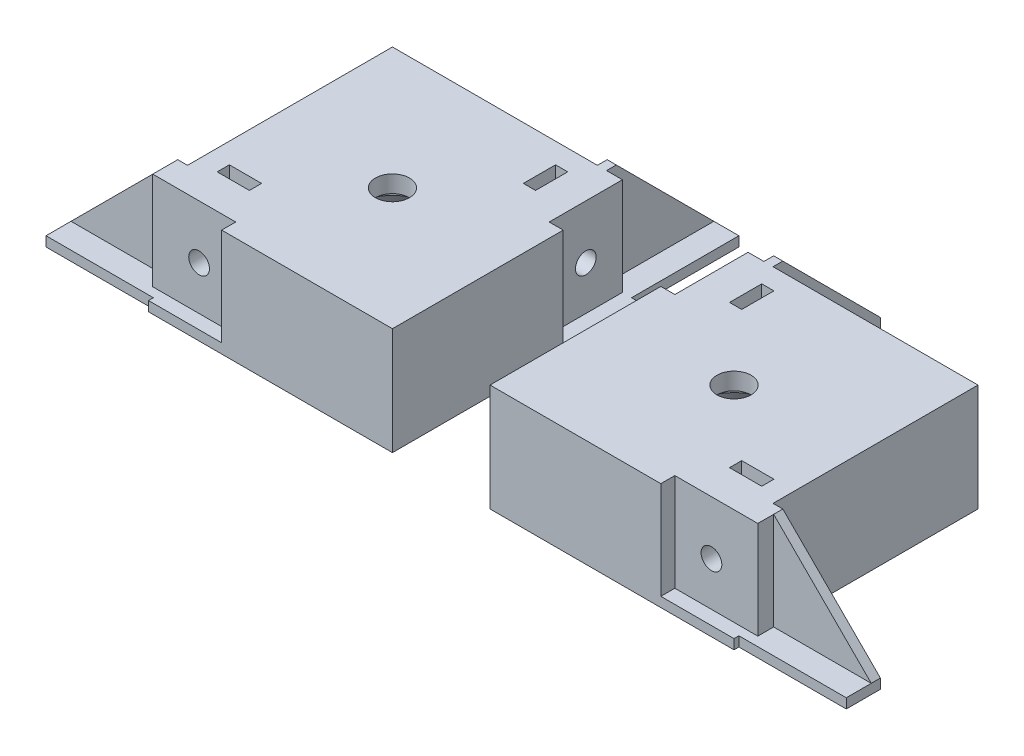
SolidWorks part; units mm, degrees
ref_plane "Front Plane" through (0, 0, 0) normal (0, 0, 1) x (1, 0, 0)
ref_plane "Top Plane" through (0, 0, 0) normal (0, 1, 0) x (1, 0, 0)
ref_plane "Right Plane" through (0, 0, 0) normal (1, 0, 0) x (0, 0, -1)
sketch "Sketch1" plane through (0, 0, 0) normal (0, 1, 0) x (1, 0, 0)
  line L0 (-25, 25) -> (25, -25) construction
  line L1 (-25, 25) -> (25, 25)
  line L2 (-25, 25) -> (-25, -25)
  line L3 (-25, -25) -> (25, -25)
  line L4 (25, 25) -> (25, -25)
  point P4 (0, 0)
  point P8 (0, 0)
  dimension "D1" = 50
extrude "Boss-Extrude1" add sketch "Sketch1" along normal blind 11 and the other way blind 11
sketch "Sketch2" plane through (0, 0, 0) normal (0, 0, 1) x (1, 0, 0)
  line L0 (-25, -11) -> (25, -11) construction
  line L1 (-3.5, 7.5) -> (-3.5, 11)
  line L2 (-3.5, 11) -> (0, 11)
  line L3 (-25, 11) -> (25, 11) construction
  line L5 (-18, -11) -> (-10.5, 4)
  line L6 (-10.5, 4) -> (-8, 4)
  line L7 (-8, 4) -> (-8, 7.5)
  line L8 (-8, 7.5) -> (-3.5, 7.5)
  line L9 (0, 11) -> (0, -11)
  line L10 (0, -11) -> (-18, -11)
  line L11 (-8, 4) -> (-8, -11) construction
  line L12 (-10.5, 4) -> (-10.5, -11) construction
  point P4 (-3.2947, 11)
  point P12 (0, 0)
  dimension "D1" = 8
  dimension "D2" = 18
  dimension "D3" = 3.5
  dimension "D4" = 2.5
  dimension "D5" = 3.5
  dimension "D6" = 3.5
revolve "Cut-Revolve1" cut sketch "Sketch2" angle 360 about L9
sketch "Sketch3" plane through (25, 0, 0) normal (1, 0, 0) x (0, 0, -1)
  line L0 (-25, 11) -> (25, 11) construction
  line L1 (-24, 11) -> (-22.125, 11)
  line L2 (-24, 11) -> (-24, -11)
  line L3 (-24, -11) -> (-17, -11)
  line L4 (-17, 11) -> (-17, -11)
  line L5 (-25, -11) -> (25, -11) construction
  line L6 (-18.875, 11) -> (-17, 11)
  line L7 (-25, -11) -> (-25, 11) construction
  line L8 (-22.125, 11) -> (-22.125, -9)
  line L9 (-22.125, -9) -> (-18.875, -9)
  line L10 (-18.875, 11) -> (-18.875, -9)
  dimension "D1" = 1
  dimension "D2" = 7
  dimension "D3" = 3.25
  dimension "D4" = 2
extrude "Boss-Extrude2" add sketch "Sketch3" along normal blind 22
sketch "Sketch4" plane through (0, 0, 17) normal (0, 0, -1) x (-1, 0, 0)
  line L0 (-47, -9) -> (-27, 11)
  line L1 (-47, -11) -> (-47, 11) construction
  line L2 (-47, 11) -> (-25, 11) construction
  line L3 (-27, 11) -> (-47, 11)
  line L4 (-47, 11) -> (-47, -9)
  dimension "D1" = 20
extrude "Cut-Extrude1" cut sketch "Sketch4" against normal blind 7
sketch "Sketch5" plane through (0, -9, 0) normal (0, 1, 0) x (1, 0, 0)
  line L1 (25, -18.875) -> (27, -18.875)
  line L2 (25, -18.875) -> (25, -22.125)
  line L3 (25, -22.125) -> (27, -22.125)
  line L4 (27, -18.875) -> (27, -22.125)
extrude "Boss-Extrude3" add sketch "Sketch5" along normal blind 20
sketch "Sketch6" plane through (0, 11, 0) normal (0, 1, 0) x (1, 0, 0)
  line L1 (47, -22.125) -> (10, -22.125)
  line L2 (47, -22.125) -> (47, -25)
  line L3 (47, -25) -> (10, -25)
  line L4 (10, -22.125) -> (10, -25)
  line L5 (-25, -25) -> (25, -25) construction
  line L6 (25, -17) -> (25, 25) construction
  point P1 (10.0363, -25)
  dimension "D1" = 15
extrude "Cut-Extrude2" cut sketch "Sketch6" against normal blind 20
sketch "Sketch8" plane through (0, 0, 22.125) normal (0, 0, 1) x (1, 0, 0)
  line L0 (0, 0) -> (17.5, 0) construction
  line L1 (25, -9) -> (17.5, 0) construction
  line L2 (17.5, 0) -> (10, -9) construction
  line L3 (27, 11) -> (10, 11) construction
  line L4 (14.2, -3.3) -> (20.8, -3.3) construction
  line L5 (14.2, -3.3) -> (14.2, 3.3) construction
  line L6 (14.2, 3.3) -> (20.8, 3.3) construction
  line L7 (20.8, -3.3) -> (20.8, 3.3) construction
  line L8 (14.2, -3.3) -> (20.8, 3.3) construction
  line L9 (14.2, 3.3) -> (20.8, -3.3) construction
  circle A0 centre (17.5, 0) radius 2.125
  dimension "D1" = 4.25
  dimension "D2" = 6.6
  dimension "D3" = 14.3
extrude "Cut-Extrude3" cut sketch "Sketch8" against normal blind 6
sketch "Sketch9" plane through (0, 11, 0) normal (0, 1, 0) x (1, 0, 0)
  line L0 (17.5, -12.625) -> (17.5, -22.125) construction
  line L1 (14.2, -12.625) -> (20.8, -12.625)
  line L2 (14.2, -12.625) -> (14.2, -15.125)
  line L3 (14.2, -15.125) -> (20.8, -15.125)
  line L4 (20.8, -12.625) -> (20.8, -15.125)
  line L7 (15.375, -22.125) -> (19.625, -22.125) construction
  line L8 (15.375, -16.125) -> (19.625, -16.125) construction
  point P6 (0, 0)
  dimension "D1" = 6.6
  dimension "D2" = 2.5
  dimension "D3" = 1
extrude "Cut-Extrude4" cut sketch "Sketch9" against normal blind 14.4
sketch "Sketch11" plane through (0, 0, 16.125) normal (0, 0, 1) x (1, 0, 0)
  circle A0 centre (17.5, 0) radius 2
  dimension "D1" = 4
extrude "Cut-Extrude5" cut sketch "Sketch11" against normal blind 8
ref_plane "Plane1" through (0, 0, 0) normal (0.7071, 0, 0.7071) x (0.7071, 0, -0.7071)
mirror "Mirror1" about plane through (0, 0, 0) normal (0.7071, 0, 0.7071) of "Cut-Extrude5", "Cut-Extrude2", "Boss-Extrude2", "Cut-Extrude1", "Cut-Extrude4", "Cut-Extrude3"
ref_plane "Plane2" through (-35, 0, 0) normal (-1, 0, 0) x (0, 0, 1)
mirror "Mirror2" about plane through (-35, 0, 0) normal (-1, 0, 0) of bodies 109
